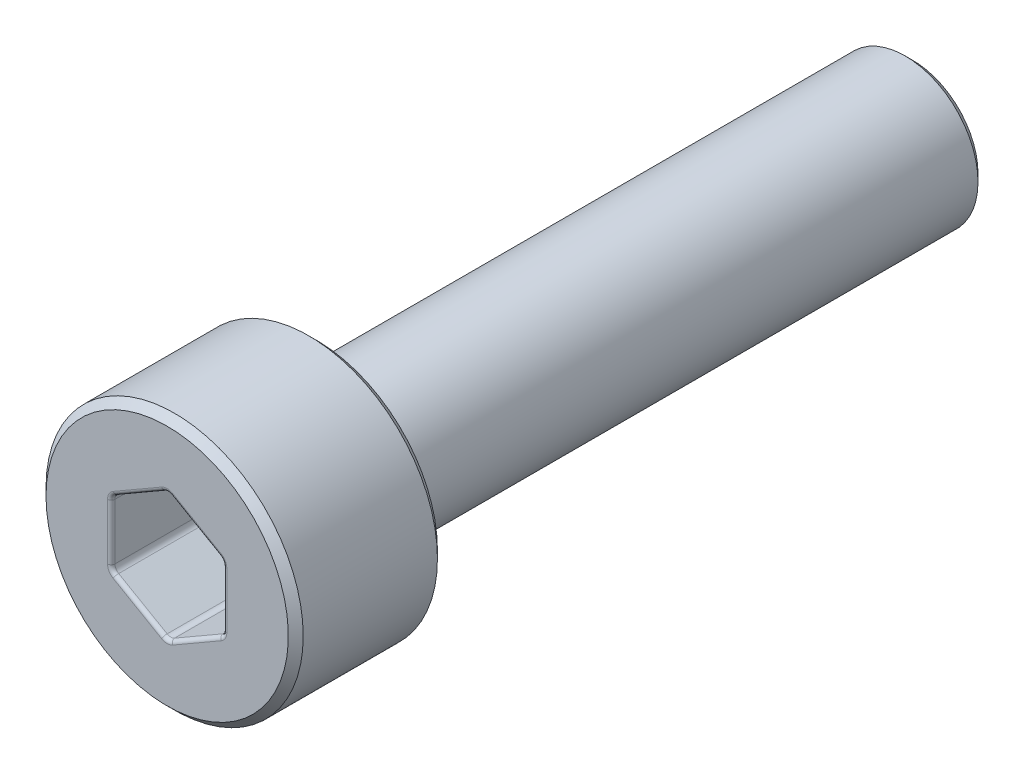
SolidWorks part; units mm, degrees
material "1.4000 (X6Cr13)"
ref_plane "Ebene vorne" through (0, 0, 0) normal (0, 0, 1) x (1, 0, 0)
ref_plane "Ebene oben" through (0, 0, 0) normal (0, 1, 0) x (1, 0, 0)
ref_plane "Ebene rechts" through (0, 0, 0) normal (1, 0, 0) x (0, 0, -1)
sketch "Skizze1" plane through (0, 0, 0) normal (1, 0, 0) x (0, 0, -1)
  line L0 (-21.9199, 0) -> (33.7608, 0) construction
  line L1 (0, 13.9907) -> (0, -9.4798) construction
  line L2 (-4, 0) -> (-4, 3.45)
  line L3 (-4, 3.45) -> (0, 3.45)
  line L4 (0, 3.45) -> (0, 1.95)
  line L5 (0, 1.95) -> (16, 1.95)
  line L6 (16, 1.95) -> (16, 0)
  line L7 (16, 0) -> (-4, 0)
  dimension "D1" = 3.9
  dimension "D2" = 4
  dimension "D3" = 6.9
  dimension "D4" = 16
revolve "Rotation1" add sketch "Skizze1" angle 360 about L0
sketch "Skizze2" plane through (0, 0, 4) normal (0, 0, 1) x (1, 0, 0)
  line L0 (0, 8.6995) -> (0, -7.3778) construction
  line L1 (1.5, -0.866) -> (1.5, 0.866)
  line L2 (1.5, 0.866) -> (0, 1.7321)
  line L3 (0, 1.7321) -> (-1.5, 0.866)
  line L4 (-1.5, 0.866) -> (-1.5, -0.866)
  line L5 (-1.5, -0.866) -> (0, -1.7321)
  line L6 (0, -1.7321) -> (1.5, -0.866)
  circle A0 centre (0, 0) radius 1.5 construction
  dimension "D1" = 3
extrude "Schnitt-Linear austragen1" cut sketch "Skizze2" against normal blind 2.5
chamfer "Fase1" distance 0.2 angle 45 3 edges at (3.45, 0, 4) (3.45, 0, 0) (1.95, 0, -16)
fillet "Verrundung1" radius 0.2 13 edges at (-0.75, -1.299, 1.5) (-1.5, 0, 1.5) (-0.75, 1.299, 1.5) (0.75, 1.299, 1.5) (1.5, 0, 1.5) (0.75, -1.299, 1.5) (-1.5, -0.866, 2.75) (0, -1.7321, 2.75) (1.5, -0.866, 2.75) (1.5, 0.866, 2.75) (0, 1.7321, 2.75) (-1.5, 0.866, 2.75) (1.95, 0, 0)
fillet "Verrundung2" radius 0.1 12 edges at (1.4732, -0.8506, 4) (0.75, -1.299, 4) (0, -1.7011, 4) (-0.75, -1.299, 4) (-1.4732, -0.8506, 4) (-1.5, 0, 4) (-1.4732, 0.8506, 4) (-0.75, 1.299, 4) (0, 1.7011, 4) (0.75, 1.299, 4) (1.4732, 0.8506, 4) (1.5, 0, 4)
ref_axis "Achse1" through (0, 0, -19.6323) along (0, 0, 1)
